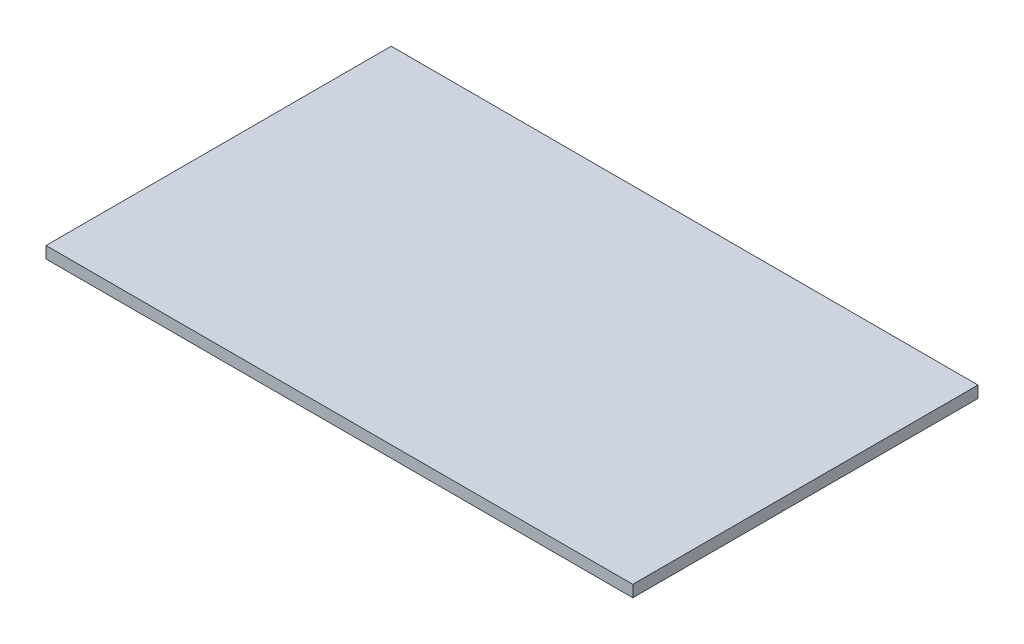
SolidWorks part; units mm, degrees
material "Hexcel AS4C (3000 Filaments)"
ref_plane "Front Plane" through (0, 0, 0) normal (0, 0, 1) x (1, 0, 0)
ref_plane "Top Plane" through (0, 0, 0) normal (0, 1, 0) x (1, 0, 0)
ref_plane "Right Plane" through (0, 0, 0) normal (1, 0, 0) x (0, 0, -1)
sketch "Sketch1" plane through (0, 0, 0) normal (0, 1, 0) x (1, 0, 0)
  line L1 (0, 0) -> (510, 0)
  line L2 (0, 0) -> (0, 300)
  line L3 (0, 300) -> (510, 300)
  line L4 (510, 0) -> (510, 300)
  dimension "D1" = 510
  dimension "D2" = 300
extrude "Boss-Extrude1" add sketch "Sketch1" along normal blind 10.16
